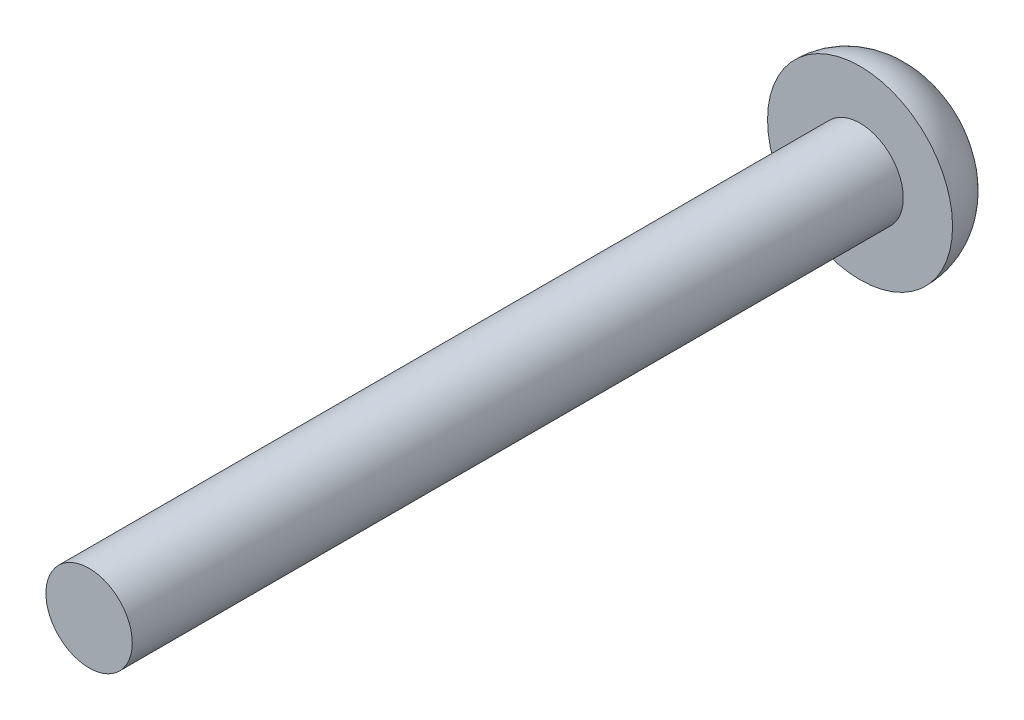
SolidWorks part; units mm, degrees
ref_plane "Plan de face" through (0, 0, 0) normal (0, 0, 1) x (1, 0, 0)
ref_plane "Plan de dessus" through (0, 0, 0) normal (0, 1, 0) x (1, 0, 0)
ref_plane "Plan de droite" through (0, 0, 0) normal (1, 0, 0) x (0, 0, -1)
sketch "Esquisse1" plane through (0, 0, 0) normal (0, 0, 1) x (1, 0, 0)
  circle A0 centre (0, 0) radius 1.4
  dimension "D1" = 2.8
extrude "Boss.-Extru.1" add sketch "Esquisse1" along normal blind 25
sketch "Esquisse2" plane through (0, 0, 0) normal (0, 0, -1) x (-1, 0, 0)
  circle A0 centre (0, 0) radius 3
  dimension "D1" = 6
extrude "Boss.-Extru.2" add sketch "Esquisse2" along normal blind 2
fillet "Congé2" radius 2 1 edges at (-3, 0, -2)
